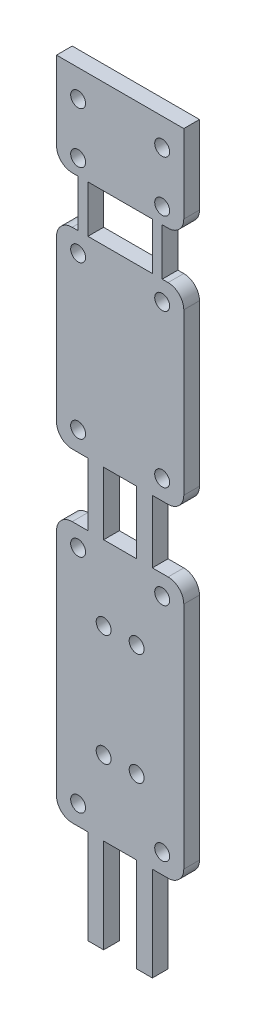
SolidWorks part; units mm, degrees
ref_plane "Front Plane" through (0, 0, 0) normal (0, 0, 1) x (1, 0, 0)
ref_plane "Top Plane" through (0, 0, 0) normal (0, 1, 0) x (1, 0, 0)
ref_plane "Right Plane" through (0, 0, 0) normal (1, 0, 0) x (0, 0, -1)
sketch "Sketch1" plane through (0, 0, 0) normal (0, 0, 1) x (1, 0, 0)
  line L0 (16.2, 1.5) -> (16.2, 14) construction
  line L1 (16.2, 109.64) -> (0, 109.64)
  line L2 (0, 109.64) -> (0, 99.66)
  line L3 (0, 1.5) -> (16.2, 1.5) construction
  line L4 (14.2, 59.21) -> (12.2, 59.21)
  line L5 (0, 14) -> (4, 14) construction
  line L6 (2, 26) -> (4, 26)
  line L7 (2, 91.66) -> (2.75, 91.66)
  line L8 (2, 67.21) -> (4, 67.21)
  line L9 (8.1, 109.64) -> (8.1, 97.66) construction
  line L10 (0, 14) -> (0, 1.5) construction
  line L11 (2, 97.66) -> (2.75, 97.66)
  line L12 (16.2, 28) -> (16.2, 57.21)
  line L13 (16.2, 99.66) -> (16.2, 109.64)
  line L14 (0, 89.66) -> (0, 69.21)
  line L15 (0, 57.21) -> (0, 28)
  line L16 (16.2, 69.21) -> (16.2, 89.66)
  line L17 (6, 14) -> (6, 26)
  line L18 (4, 59.21) -> (4, 67.21)
  line L19 (4, 14) -> (4, 26)
  line L20 (6, 59.21) -> (6, 67.21)
  line L21 (4, 91.66) -> (4, 97.66)
  line L22 (2.75, 97.66) -> (2.75, 91.66)
  line L23 (10.2, 14) -> (10.2, 26)
  line L24 (12.2, 14) -> (12.2, 26)
  line L25 (10.2, 59.21) -> (10.2, 67.21)
  line L26 (12.2, 59.21) -> (12.2, 67.21)
  line L27 (13.45, 91.66) -> (13.45, 97.66)
  line L28 (12.2, 91.66) -> (12.2, 97.66)
  line L29 (4, 97.66) -> (12.2, 97.66)
  line L30 (4, 91.66) -> (12.2, 91.66)
  line L31 (13.45, 91.66) -> (14.2, 91.66)
  line L32 (13.45, 97.66) -> (14.2, 97.66)
  line L33 (6, 67.21) -> (10.2, 67.21)
  line L34 (12.2, 67.21) -> (14.2, 67.21)
  line L35 (10.2, 59.21) -> (6, 59.21)
  line L36 (4, 59.21) -> (2, 59.21)
  line L37 (6, 14) -> (10.2, 14) construction
  line L38 (6, 26) -> (10.2, 26)
  line L39 (12.2, 26) -> (14.2, 26)
  line L40 (12.2, 14) -> (16.2, 14) construction
  line L41 (12.2, 14) -> (10.2, 14)
  line L42 (6, 14) -> (4, 14)
  circle A0 centre (13.45, 56.71) radius 0.95
  circle A1 centre (10.2, 49.71) radius 0.95
  circle A2 centre (13.45, 106.16) radius 0.95
  circle A3 centre (2.75, 99.66) radius 0.95
  circle A4 centre (6, 49.71) radius 0.95
  circle A5 centre (2.75, 28.5) radius 0.95
  circle A6 centre (2.75, 89.16) radius 0.95
  circle A7 centre (2.75, 56.71) radius 0.95
  circle A8 centre (13.45, 89.16) radius 0.95
  circle A9 centre (13.45, 99.66) radius 0.95
  arc A10 (16.2, 28) -> (14.2, 26) centre (14.2, 28) cw
  arc A11 (0, 28) -> (2, 26) centre (2, 28) ccw
  arc A12 (16.2, 57.21) -> (14.2, 59.21) centre (14.2, 57.21) ccw
  arc A13 (0, 57.21) -> (2, 59.21) centre (2, 57.21) cw
  arc A14 (16.2, 69.21) -> (14.2, 67.21) centre (14.2, 69.21) cw
  arc A15 (0, 69.21) -> (2, 67.21) centre (2, 69.21) ccw
  arc A16 (0, 89.66) -> (2, 91.66) centre (2, 89.66) cw
  arc A17 (16.2, 89.66) -> (14.2, 91.66) centre (14.2, 89.66) ccw
  arc A18 (16.2, 99.66) -> (14.2, 97.66) centre (14.2, 99.66) cw
  arc A19 (2, 97.66) -> (0, 99.66) centre (2, 99.66) cw
  circle A28 centre (13.45, 69.71) radius 0.95
  circle A29 centre (6, 35.5) radius 0.95
  circle A32 centre (2.75, 106.16) radius 0.95
  circle A33 centre (10.2, 35.5) radius 0.95
  circle A34 centre (2.75, 69.71) radius 0.95
  circle A35 centre (13.45, 28.5) radius 0.95
  circle A36 centre (2.85, 11.5) radius 0.95 construction
  circle A37 centre (13.35, 11.5) radius 0.95 construction
  circle A38 centre (13.35, 5.5) radius 0.95 construction
  circle A39 centre (2.85, 5.5) radius 0.95 construction
  point P71 (16.2, 26)
  point P74 (0, 26)
  point P91 (16.2, 59.21)
  point P94 (0, 59.21)
  point P97 (16.2, 67.21)
  point P100 (0, 67.21)
  point P103 (0, 91.66)
  point P106 (16.2, 91.66)
  point P109 (16.2, 97.66)
  point P112 (0, 97.66)
  dimension "D45" = 1.9
  dimension "D46" = 2
  dimension "D1" = 4
  dimension "D2" = 4
  dimension "D3" = 2.85
  dimension "D4" = 2.85
  dimension "D5" = 16.2
  dimension "D6" = 6
  dimension "D7" = 6
  dimension "D8" = 2.85
  dimension "D9" = 2.85
  dimension "D10" = 2.5
  dimension "D11" = 12
  dimension "D12" = 33.21
  dimension "D13" = 2.5
  dimension "D14" = 2.5
  dimension "D15" = 2.75
  dimension "D16" = 2.75
  dimension "D17" = 2.5
  dimension "D18" = 2.5
  dimension "D19" = 2.75
  dimension "D20" = 2.75
  dimension "D21" = 9.5
  dimension "D22" = 6
  dimension "D23" = 9.5
  dimension "D24" = 6
  dimension "D25" = 9.5
  dimension "D26" = 9.5
  dimension "D27" = 6
  dimension "D28" = 6
  dimension "D29" = 8
  dimension "D30" = 24.45
  dimension "D31" = 2.5
  dimension "D32" = 2.5
  dimension "D33" = 2.75
  dimension "D34" = 2.75
  dimension "D35" = 6
  dimension "D36" = 2.75
  dimension "D37" = 2
  dimension "D38" = 2.75
  dimension "D39" = 8.5
  dimension "D40" = 11.98
  dimension "D41" = 2.5
  dimension "D42" = 2.5
  dimension "D43" = 2.75
  dimension "D44" = 2.75
extrude "Boss-Extrude1" add sketch "Sketch1" along normal blind 2
sketch "Sketch2" plane through (0, 0, 0) normal (0, 0, -1) x (-1, 0, 0)
  line L0 (-13.45, 97.66) -> (-2.75, 97.66)
  line L1 (-2.75, 97.66) -> (-2.75, 91.66)
  line L2 (-2.75, 91.66) -> (-13.45, 91.66)
  line L3 (-13.45, 91.66) -> (-13.45, 97.66)
  line L4 (-12.2, 67.21) -> (-4, 67.21)
  line L5 (-4, 67.21) -> (-4, 59.21)
  line L6 (-4, 59.21) -> (-12.2, 59.21)
  line L7 (-12.2, 59.21) -> (-12.2, 67.21)
  line L8 (-12.2, 26) -> (-4, 26)
  line L9 (-4, 26) -> (-4, 14)
  line L10 (-4, 14) -> (-12.2, 14)
  line L11 (-12.2, 14) -> (-12.2, 26)
extrude "Cut-Extrude1" [suppressed] cut sketch "Sketch2" against normal up to surface (2 mm away) up to face at (3.7, 69.71, 2)
equation "\"D12@Sketch1\"= \"HL@parametersSketch@prostheticParameters.SLDPRT\" * 0.266 - 12 - 4 'Middle PIP Length"
equation "\"D30@Sketch1\"= \"HL@parametersSketch@prostheticParameters.SLDPRT\" * 0.17 - 4 - 3'Middle MIP Length"
equation "\"D5@Sketch1\"= \"fingerWidth@parametersSketch@prostheticParameters.SLDPRT\" 'Middle Width"
equation "\"D40@Sketch1\"= \"HL@parametersSketch@prostheticParameters.SLDPRT\" * 0.108 - 3 - 5'Middle DIP Length"
equation "\"D45@Sketch1\"= 1.5 + \"tol1@parametersSketch@prostheticParameters.SLDPRT\""
